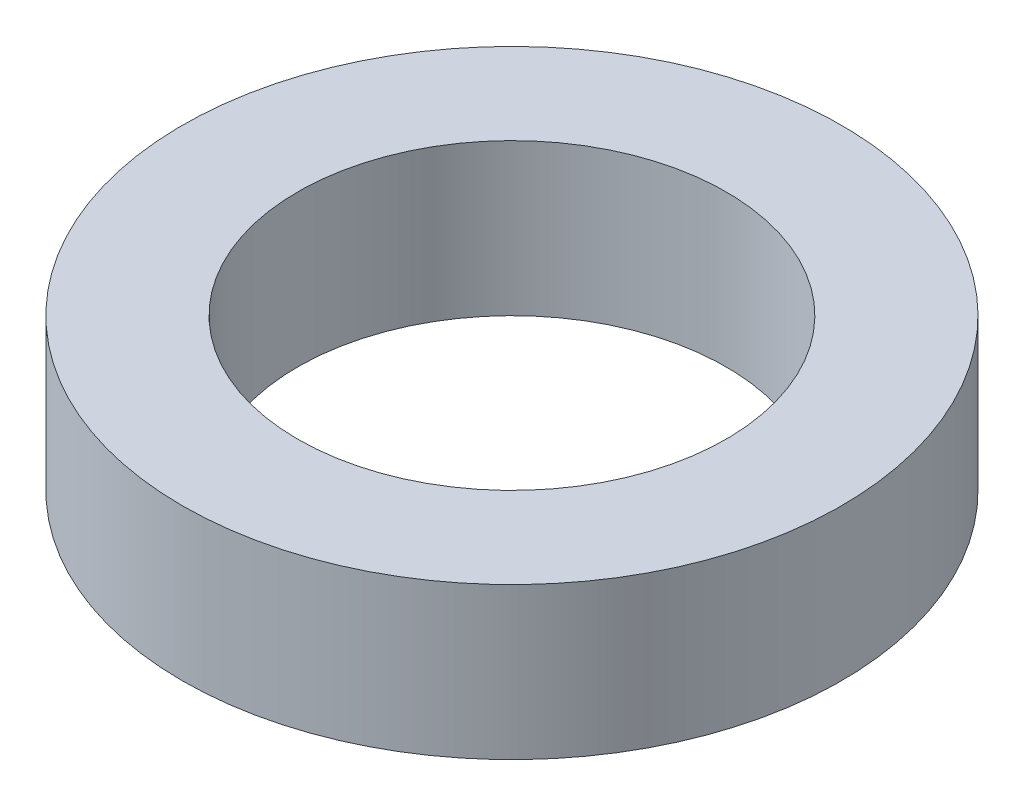
SolidWorks part; units mm, degrees
ref_plane "Front Plane" through (0, 0, 0) normal (0, 0, 1) x (1, 0, 0)
ref_plane "Top Plane" through (0, 0, 0) normal (0, 1, 0) x (1, 0, 0)
ref_plane "Right Plane" through (0, 0, 0) normal (1, 0, 0) x (0, 0, -1)
sketch "Sketch1" plane through (0, 0, 0) normal (0, 1, 0) x (1, 0, 0)
  circle A0 centre (0, 0) radius 50
  dimension "FLANGE_OD" = 100
extrude "Boss-Extrude1" add sketch "Sketch1" along normal blind 23
sketch "Sketch2" plane through (0, 0, 0) normal (0, 1, 0) x (1, 0, 0)
  circle A0 centre (0, 0) radius 32.5
  dimension "BORE_D" = 65
extrude "Cut-Extrude1" cut sketch "Sketch2" along normal through all
sketch "Sketch3" plane through (0, 23, 0) normal (0, 1, 0) x (1, 0, 0)
  circle A0 centre (0, 0) radius 22.4309 construction
  circle A1 centre (-22.4309, 0) radius 2.1993
  dimension "BOLT_D" = 4.3986
  dimension "BOLT_PCD" = 44.8618
extrude "Cut-Extrude2" cut sketch "Sketch3" against normal blind 21.5181 rebuild error yes
pattern_circular "CirPattern1" count 4 over 360 rebuild error yes
